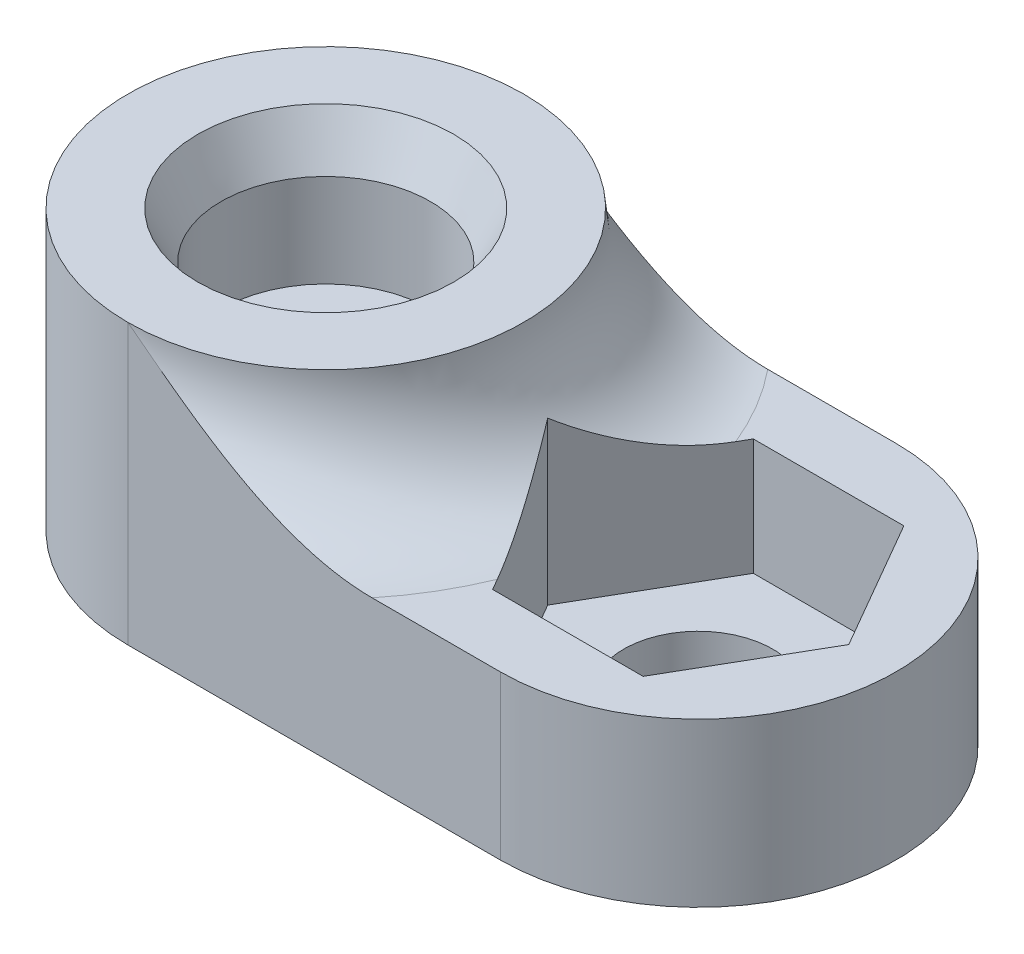
SolidWorks part; units mm, degrees
ref_plane "Front Plane" through (0, 0, 0) normal (0, 0, 1) x (1, 0, 0)
ref_plane "Top Plane" through (0, 0, 0) normal (0, 1, 0) x (1, 0, 0)
ref_plane "Right Plane" through (0, 0, 0) normal (1, 0, 0) x (0, 0, -1)
sketch "Sketch1" plane through (0, 0, 0) normal (0, 1, 0) x (1, 0, 0)
  line L0 (-4, 0) -> (4, 0) construction
  line L1 (-4, 4.25) -> (4, 4.25)
  line L2 (-4, -4.25) -> (4, -4.25)
  arc A0 (-4, 4.25) -> (-4, -4.25) centre (-4, 0) ccw
  arc A1 (4, -4.25) -> (4, 4.25) centre (4, 0) ccw
  point P2 (0, 0)
  dimension "D1" = 8
  dimension "D2" = 8.5
extrude "Boss-Extrude1" add sketch "Sketch1" along normal blind 6
sketch "Sketch2" plane through (0, 6, 0) normal (0, 1, 0) x (1, 0, 0)
  circle A0 centre (-4, 0) radius 2.25
  arc A1 (-4, 4.25) -> (-4, -4.25) centre (-4, 0) ccw construction
  dimension "D1" = 4.5
extrude "Cut-Extrude1" cut sketch "Sketch2" against normal blind 3
sketch "Sketch3" plane through (0, 0, 0) normal (0, -1, 0) x (1, 0, 0)
  circle A0 centre (-4, 0) radius 2.5
  arc A1 (-4, 4.25) -> (-4, -4.25) centre (-4, 0) ccw construction
  dimension "D1" = 5
extrude "Cut-Extrude2" cut sketch "Sketch3" against normal blind 1.5
sketch "Sketch4" plane through (0, 3, 0) normal (0, 1, 0) x (1, 0, 0)
  circle A0 centre (-4, 0) radius 1.35
  dimension "D1" = 2.7
extrude "Cut-Extrude3" cut sketch "Sketch4" against normal through all
sketch "Sketch5" plane through (0, 6, 0) normal (0, 1, 0) x (1, 0, 0)
  line L1 (7.2332, 0) -> (5.6166, 2.8)
  line L2 (5.6166, 2.8) -> (2.3834, 2.8)
  line L3 (2.3834, 2.8) -> (0.7668, 0)
  line L4 (0.7668, 0) -> (2.3834, -2.8)
  line L5 (2.3834, -2.8) -> (5.6166, -2.8)
  line L6 (5.6166, -2.8) -> (7.2332, 0)
  circle A0 centre (4, 0) radius 2.8 construction
  arc A1 (4, -4.25) -> (4, 4.25) centre (4, 0) ccw construction
  dimension "D1" = 5.6
extrude "Cut-Extrude4" cut sketch "Sketch5" against normal blind 5
sketch "Sketch6" plane through (0, 1, 0) normal (0, 1, 0) x (1, 0, 0)
  circle A0 centre (4, 0) radius 1.6
  arc A1 (4, -4.25) -> (4, 4.25) centre (4, 0) ccw construction
  dimension "D1" = 3.2
extrude "Cut-Extrude5" cut sketch "Sketch6" against normal through all
chamfer "Chamfer2" distance 0.5 distance2 1 1 edges at (-4, 6, 2.25) first distance on face at (4, 6, 0)
sketch "Sketch8" plane through (0, 6, 0) normal (0, 1, 0) x (1, 0, 0)
  line L0 (4, 4.25) -> (-4, 4.25) construction
  line L1 (-4, -4.25) -> (4, -4.25) construction
  line L2 (4, 4.25) -> (-4, 4.25)
  line L3 (-4, -4.25) -> (4, -4.25)
  arc A0 (4, -4.25) -> (4, 4.25) centre (4, 0) ccw construction
  arc A1 (4, -4.25) -> (4, 4.25) centre (4, 0) ccw
  arc A2 (-4, 4.25) -> (-4, -4.25) centre (-4, 0) cw
  arc A3 (-4, 4.25) -> (-4, -4.25) centre (-4, 0) ccw construction
extrude "Cut-Extrude6" cut sketch "Sketch8" against normal blind 2.5
fillet "Fillet1" radius 2.5 1 edges at (0.25, 3.5, 0)
chamfer "Chamfer3" distance 1.25 distance2 1 1 edges at (-4, 1.5, -1.35) first distance on face at (-4, 1.5, -1.35)
